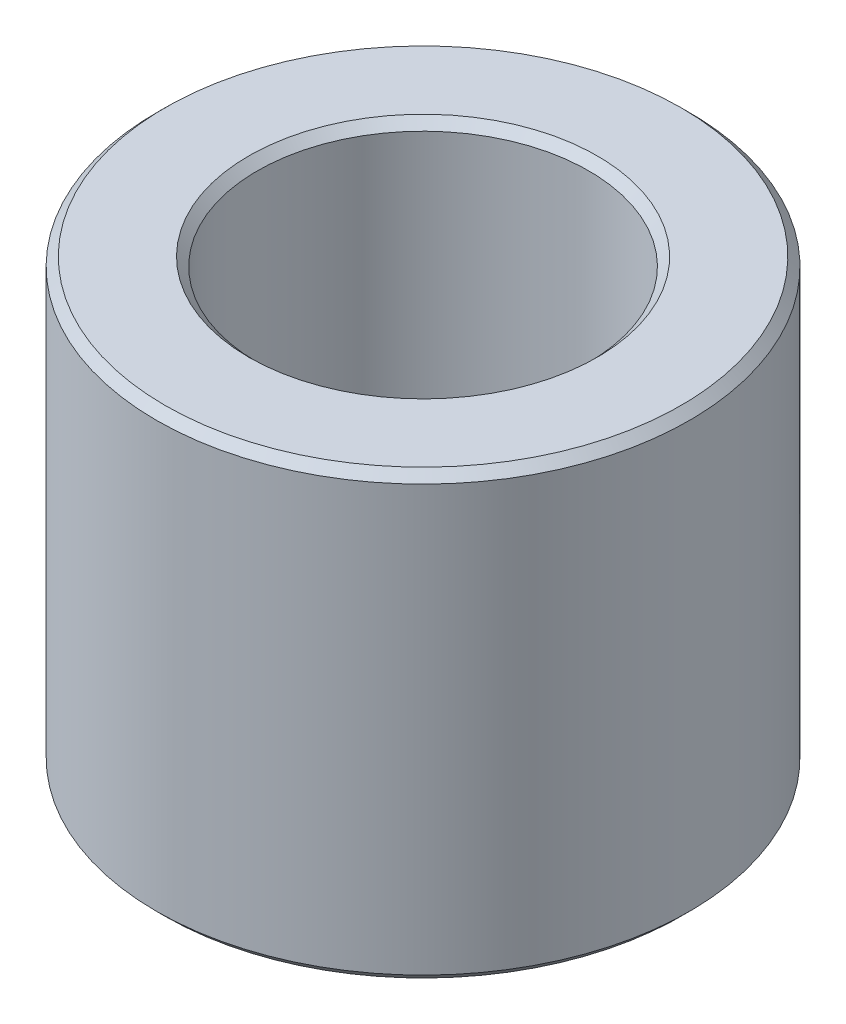
SolidWorks part; units mm, degrees
ref_plane "Front Plane" through (0, 0, 0) normal (0, 0, 1) x (1, 0, 0)
ref_plane "Top Plane" through (0, 0, 0) normal (0, 1, 0) x (1, 0, 0)
ref_plane "Right Plane" through (0, 0, 0) normal (1, 0, 0) x (0, 0, -1)
sketch "Sketch1" plane through (0, 0, 0) normal (0, 1, 0) x (1, 0, 0)
  circle A0 centre (0, 0) radius 35
  dimension "SLEEVE_OD" = 70
extrude "Boss-Extrude1" add sketch "Sketch1" along normal blind 58.0948
sketch "Sketch2" plane through (0, 0, 0) normal (0, 1, 0) x (1, 0, 0)
  circle A0 centre (0, 0) radius 21.7642
  dimension "BORE_D" = 43.5283
extrude "Cut-Extrude1" cut sketch "Sketch2" along normal through all
chamfer "Chamfer1" distance 1.1306 angle 45 4 edges at (0, 58.0948, 21.7642) (0, 0, 21.7642) (0, 0, 35) (0, 58.0948, 35)
